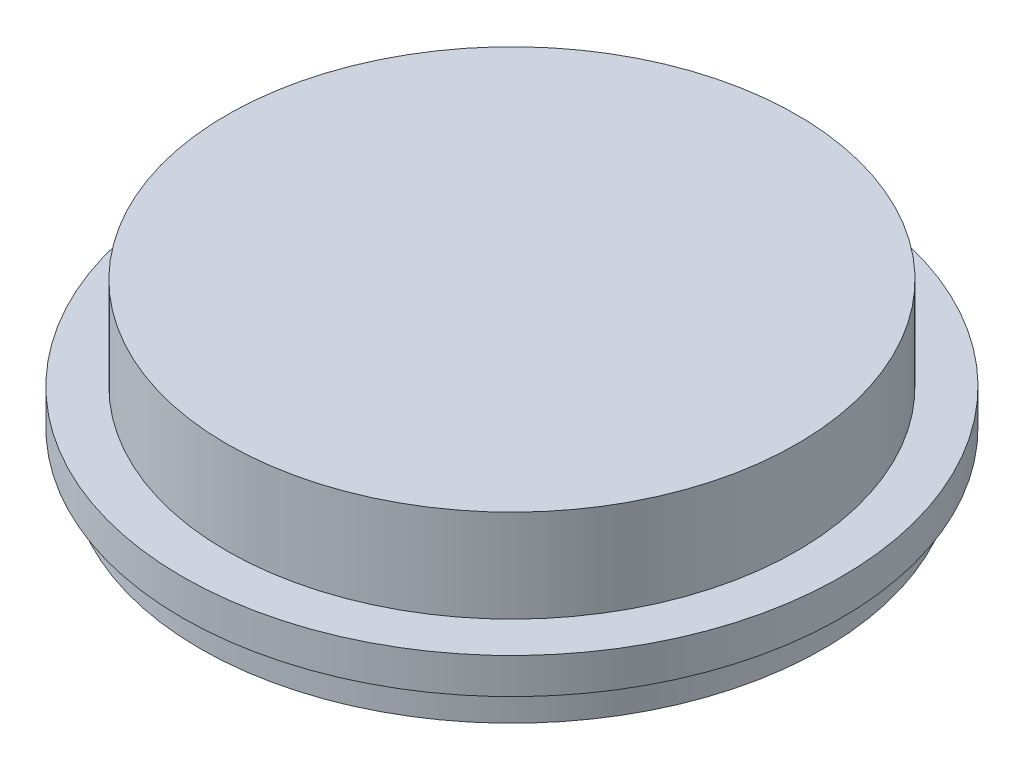
SolidWorks part; units mm, degrees
material "Epoxy, Unfilled"
ref_plane "Front Plane" through (0, 0, 0) normal (0, 0, 1) x (1, 0, 0)
ref_plane "Top Plane" through (0, 0, 0) normal (0, 1, 0) x (1, 0, 0)
ref_plane "Right Plane" through (0, 0, 0) normal (1, 0, 0) x (0, 0, -1)
sketch "Sketch1" plane through (0, 0, 0) normal (0, 0, 1) x (1, 0, 0)
  line L0 (0, 3.81) -> (0, -12.7) construction
  line L1 (58.7375, 0) -> (58.7375, -6.35)
  line L2 (58.7375, -6.35) -> (55.5625, -6.35)
  line L3 (55.5625, -6.35) -> (55.5625, -12.7)
  line L4 (55.5625, -12.7) -> (49.2125, -12.7)
  line L5 (49.2125, -12.7) -> (49.2125, -6.35)
  line L10 (58.7375, 0) -> (50.8, 0)
  line L11 (50.8, 0) -> (50.8, 16.51)
  line L12 (50.8, 16.51) -> (0, 16.51)
  line L13 (0, 16.51) -> (0, 10.16)
  line L14 (0, 10.16) -> (44.45, 10.16)
  line L15 (44.45, 10.16) -> (44.45, -6.35)
  line L16 (44.45, -6.35) -> (49.2125, -6.35)
  dimension "D1" = 58.7375
  dimension "D2" = 3.175
  dimension "D3" = 6.35
  dimension "D4" = 6.35
  dimension "D5" = 6.35
revolve "Revolve1" add sketch "Sketch1" angle 360 about L0 region at (58.0815, -3.175, 0)
